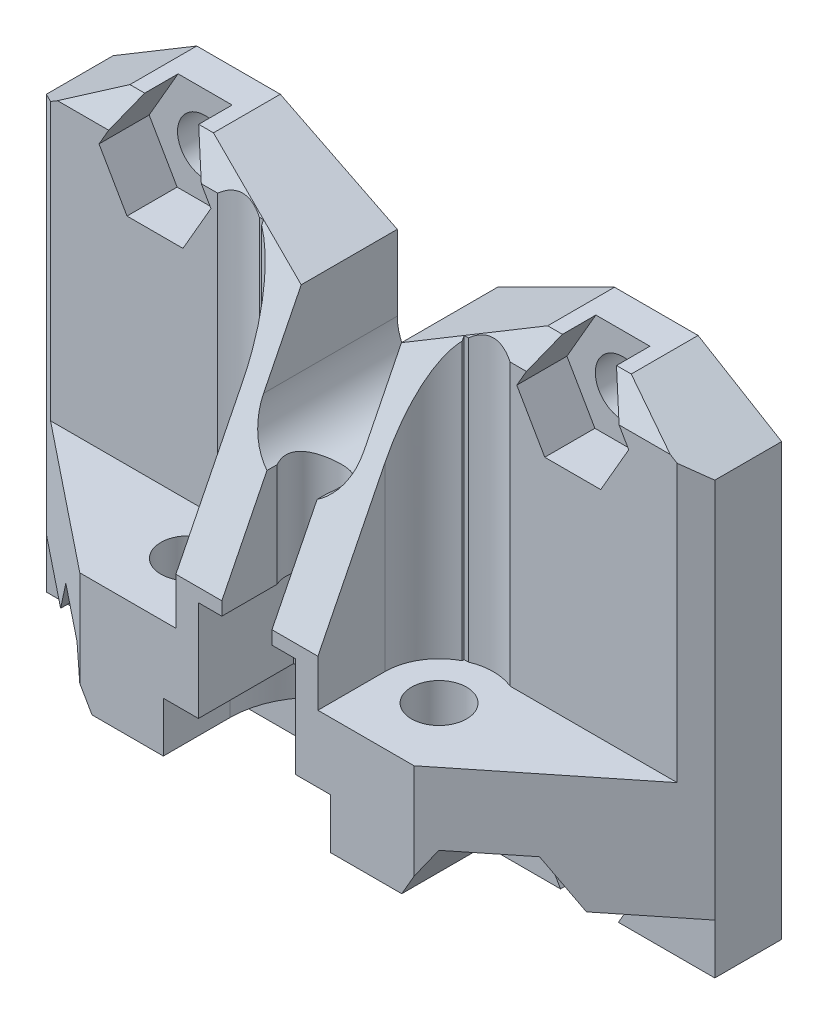
SolidWorks part; units mm, degrees
ref_plane "Front Plane" through (0, 0, 0) normal (0, 0, 1) x (1, 0, 0)
ref_plane "Top Plane" through (0, 0, 0) normal (0, 1, 0) x (1, 0, 0)
ref_plane "Right Plane" through (0, 0, 0) normal (1, 0, 0) x (0, 0, -1)
sketch "Sketch1" plane through (0, 0, 0) normal (0, 0, 1) x (1, 0, 0)
  line L1 (-20, 0) -> (20, 0)
  line L2 (-20, 0) -> (-20, 28.8)
  line L3 (-20, 28.8) -> (20, 28.8)
  line L4 (20, 0) -> (20, 28.8)
  dimension "D2" = 40
  dimension "D3" = 28.8
extrude "Boss-Extrude1" add sketch "Sketch1" along normal blind 12
chamfer "Chamfer2" distance 8 distance2 16 1 edges at (0, 28.8, 12) first distance on face at (0, 28.8, 6)
sketch "Sketch10" plane through (0, 0, 12) normal (0, 0, 1) x (1, 0, 0)
  line L0 (-6, 28.8) -> (-6, 10)
  line L2 (-6, 10) -> (-20, 10)
  line L3 (-20, 12.8) -> (-20, 0) construction
  line L4 (0, 0) -> (0, 29.2248) construction
  line L5 (-6, 28.8) -> (-20, 28.8)
  line L6 (-20, 28.8) -> (-20, 10)
  line L7 (20, 28.8) -> (20, 10)
  line L8 (6, 28.8) -> (20, 28.8)
  line L9 (6, 10) -> (20, 10)
  line L10 (6, 28.8) -> (6, 10)
  line L11 (-20, 28.8) -> (20, 28.8) construction
  dimension "D1" = 10
  dimension "D2" = 6
extrude "Cut-Extrude7" cut sketch "Sketch10" against normal offset from surface (7 mm away) 5 up to face at (0, 14.4, 0)
sketch "Sketch11" plane through (0, 0, 12) normal (0, 0, 1) x (1, 0, 0)
  line L0 (20, 0) -> (20, 10) construction
  line L1 (-20, 0) -> (20, 0)
  line L2 (-20, 0) -> (-20, 3)
  line L3 (-20, 3) -> (20, 3)
  line L4 (20, 0) -> (20, 3)
  dimension "D1" = 3
extrude "Cut-Extrude8" cut sketch "Sketch11" against normal blind 8
chamfer "Chamfer3" distance 8 distance2 10 2 edges at (-20, 6.5, 12) (20, 6.5, 12) first distance on face at (-20, 12.2667, 5.1111) first distance on face at (20, 12.2667, 5.1111)
sketch "Sketch12" plane through (0, 28.8, 0) normal (0, 1, 0) x (1, 0, 0)
  line L0 (0, 0) -> (0, -14.4613) construction
  line L1 (-4.25, -8) -> (-4.25, -12)
  line L2 (-4.25, -12) -> (-10.75, -12)
  line L3 (-10, -12) -> (-6, -12) construction
  line L4 (-10.75, -12) -> (-10.75, -8)
  line L5 (6, -12) -> (-6, -12) construction
  arc A0 (-4.25, -8) -> (-10.75, -8) centre (-7.5, -8) ccw
  dimension "D1" = 3.25
  dimension "D2" = 8
  dimension "D3" = 7.5
extrude "Cut-Extrude9" cut sketch "Sketch12" against normal up to surface (18.8 mm away) up to face at (-10.1875, 10, 8.5)
sketch "Sketch13" plane through (0, 10, 0) normal (0, 1, 0) x (1, 0, 0)
  circle A0 centre (-7.5, -8) radius 1.65
  arc A1 (-4.25, -8) -> (-6, -5.1169) centre (-7.5, -8) ccw construction
  dimension "D1" = 3.3
extrude "Cut-Extrude10" cut sketch "Sketch13" against normal through all
sketch "Sketch3" plane through (0, 0, 0) normal (0, -1, 0) x (1, 0, 0)
  line L0 (0, 0) -> (0, 12) construction
  line L1 (-20, 12) -> (20, 12) construction
  line L2 (-5, 8) -> (-5, 12)
  line L3 (5, 8) -> (5, 12)
  line L4 (-5, 12) -> (5, 12)
  line L5 (-20, 0) -> (20, 0) construction
  arc A0 (-5, 8) -> (5, 8) centre (0, 8) ccw
  dimension "D1" = 8
  dimension "D2" = 10
extrude "Cut-Extrude2" cut sketch "Sketch3" against normal blind 6
sketch "Sketch4" plane through (0, 0, 12) normal (0, 0, 1) x (1, 0, 0)
  line L0 (0, 28.8) -> (0, 14.0803) construction
  line L1 (20, 28.8) -> (-20, 28.8) construction
  line L2 (-3, 20.8) -> (-3, 28.8)
  line L3 (3, 20.8) -> (3, 28.8)
  line L4 (-3, 28.8) -> (3, 28.8)
  arc A0 (-3, 20.8) -> (3, 20.8) centre (0, 20.8) ccw
  dimension "D1" = 8
  dimension "D2" = 6
extrude "Cut-Extrude3" cut sketch "Sketch4" against normal through all
sketch "Sketch2" plane through (0, 0, 12) normal (0, 0, 1) x (1, 0, 0)
  line L0 (0, 0) -> (0, 28.8) construction
  line L1 (20, 28.8) -> (-20, 28.8) construction
  line L2 (-12.5, 2.8) -> (12.5, 2.8) construction
  line L3 (-12.5, 25.8) -> (12.5, 25.8) construction
  line L4 (-12.5, 25.8) -> (-12.5, 2.8) construction
  circle A0 centre (-12.5, 2.8) radius 1.65
  circle A1 centre (12.5, 2.8) radius 1.65
  circle A2 centre (12.5, 25.8) radius 1.65
  circle A3 centre (-12.5, 25.8) radius 1.65
  dimension "D5" = 3.3
  dimension "D1" = 25
  dimension "D2" = 23
  dimension "D3" = 2.8
  dimension "D4" = 12.5
extrude "Cut-Extrude1" cut sketch "Sketch2" against normal through all
sketch "Sketch5" plane through (0, 0, 12) normal (0, 0, 1) x (1, 0, 0)
  line L0 (-13.804, 29.3415) -> (-11.196, 29.3415)
  line L1 (-9.1514, 25.8) -> (-11.196, 29.3415)
  line L2 (11.196, 29.3415) -> (13.804, 29.3415)
  line L3 (-13.804, 29.3415) -> (-15.8486, 25.8)
  line L4 (-15.8486, 25.8) -> (-14.1743, 22.9)
  line L5 (-14.1743, 22.9) -> (-10.8257, 22.9)
  line L6 (-10.8257, 22.9) -> (-9.1514, 25.8)
  line L7 (-9.1514, 2.8) -> (-10.8257, 5.7)
  line L8 (-10.8257, 5.7) -> (-14.1743, 5.7)
  line L9 (-14.1743, 5.7) -> (-15.8486, 2.8)
  line L10 (-15.8486, 2.8) -> (-14.1743, -0.1)
  line L11 (-14.1743, -0.1) -> (-10.8257, -0.1)
  line L12 (-10.8257, -0.1) -> (-9.1514, 2.8)
  line L13 (15.8486, 2.8) -> (14.1743, 5.7)
  line L14 (14.1743, 5.7) -> (10.8257, 5.7)
  line L15 (10.8257, 5.7) -> (9.1514, 2.8)
  line L16 (9.1514, 2.8) -> (10.8257, -0.1)
  line L17 (10.8257, -0.1) -> (14.1743, -0.1)
  line L18 (14.1743, -0.1) -> (15.8486, 2.8)
  line L19 (15.8486, 25.8) -> (13.804, 29.3415)
  line L21 (11.196, 29.3415) -> (9.1514, 25.8)
  line L22 (9.1514, 25.8) -> (10.8257, 22.9)
  line L23 (10.8257, 22.9) -> (14.1743, 22.9)
  line L24 (14.1743, 22.9) -> (15.8486, 25.8)
  line L26 (-10.8257, 28.7) -> (-14.1743, 28.7) [skipped]
  line L27 (14.1743, 28.7) -> (10.8257, 28.7) [skipped]
  circle A0 centre (-12.5, 25.8) radius 2.9 construction
  circle A1 centre (-12.5, 2.8) radius 2.9 construction
  circle A2 centre (12.5, 2.8) radius 2.9 construction
  circle A3 centre (12.5, 25.8) radius 2.9 construction
  dimension "D1" = 5.8
extrude "Cut-Extrude4" cut sketch "Sketch5" against normal offset from surface (10 mm away) 2 up to face at (-10.85, 25.8, 0)
sketch "Sketch6" plane through (0, 6, 0) normal (0, -1, 0) x (1, 0, 0)
  line L0 (0, 0) -> (0, 12) construction
  line L1 (5, 12) -> (-5, 12) construction
  line L2 (-2.9, 12) -> (2.9, 12)
  line L3 (0, 4.6514) -> (2.9, 6.3257)
  line L4 (2.9, 6.3257) -> (2.9, 12)
  line L7 (-2.9, 12) -> (-2.9, 6.3257)
  line L8 (-2.9, 6.3257) -> (0, 4.6514)
  line L10 (0, 11.3486) -> (-2.9, 9.6743) [skipped]
  line L11 (2.9, 9.6743) -> (0, 11.3486) [skipped]
  circle A0 centre (0, 8) radius 2.9 construction
  dimension "D2" = 5.8
  dimension "D1" = 8
extrude "Cut-Extrude5" cut sketch "Sketch6" against normal blind 6
sketch "Sketch7" plane through (0, 12, 0) normal (0, -1, 0) x (1, 0, 0)
  line L0 (0, 0) -> (0, 12) construction
  line L1 (2.9, 12) -> (-2.9, 12) construction
  line L2 (-1.5, 8.6874) -> (-1.5, 12)
  line L3 (-1.5, 12) -> (1.5, 12)
  line L4 (1.5, 12) -> (1.5, 8.6874)
  arc A0 (-1.5, 8.6874) -> (1.5, 8.6874) centre (0, 8) ccw
  dimension "D1" = 3.3
  dimension "D2" = 8
  dimension "D3" = 3
  dimension "D4" = 1.5
extrude "Cut-Extrude6" cut sketch "Sketch7" against normal through all
mirror "Mirror1" about plane through (0, 0, 0) normal (1, 0, 0) of "Cut-Extrude10", "Cut-Extrude9"
chamfer "Chamfer4" distance 3 distance2 5 1 edges at (20, 28.8, 2) first distance on face at (20, 12.12, 2.4)
chamfer "Chamfer5" distance 5 distance2 3 1 edges at (-20, 28.8, 2) first distance on face at (-12, 28.8, 2.5)
chamfer "Chamfer6" distance 7 distance2 3.5 1 edges at (-3, 28.8, 2) tangent propagation no first distance on face at (-10.75, 28.8, 2.5)
chamfer "Chamfer7" distance 3.5 distance2 7 1 edges at (3, 28.8, 2) first distance on face at (3, 24.8, 3)
